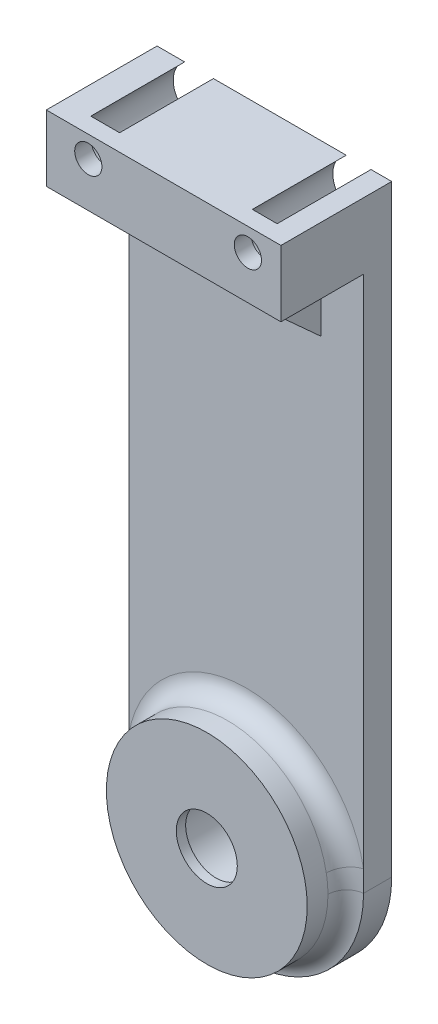
SolidWorks part; units mm, degrees
ref_plane "Plano frontal" through (0, 0, 0) normal (0, 0, 1) x (1, 0, 0)
ref_plane "Plano superior" through (0, 0, 0) normal (0, 1, 0) x (1, 0, 0)
ref_plane "Plano direito" through (0, 0, 0) normal (1, 0, 0) x (0, 0, -1)
ref_plane "Plano1" through (0, 0, -1.35) normal (0, 0, 1) x (1, 0, 0)
sketch "Esboço2" plane through (0, 0, -1.35) normal (0, 0, 1) x (1, 0, 0)
  circle A5 centre (-0.4749, -0.0634) radius 10.7 construction
  circle A6 centre (-0.4749, -0.0634) radius 10.7
extrude "Ressalto-extrusão1" add sketch "Esboço2" against normal offset from surface (4.2 mm away) 2 offset beyond the face yes
sketch "Esboço4" plane through (0, 0, -5.55) normal (0, 0, -1) x (-1, 0, 0)
  line L0 (-12.0251, -0.0634) -> (-12.0251, 64.1202)
  line L1 (12.9749, -0.0634) -> (12.9749, 64.1202)
  line L2 (12.9749, 64.1202) -> (-12.0251, 64.1202)
  arc A0 (-12.0251, -0.0634) -> (12.9749, -0.0634) centre (0.4749, -0.0634) ccw
  arc A2 (-12.0247, -0.1594) -> (12.9746, 0.0325) centre (0.4749, -0.0634) ccw construction
  dimension "D1" = 0.5
extrude "Ressalto-extrusão3" add sketch "Esboço4" along normal blind 3
sketch "Esboço5" plane through (0, 0, -8.55) normal (0, 0, -1) x (-1, 0, 0)
  line L0 (12.9749, -0.0634) -> (12.9749, 64.1202) construction
  line L1 (-12.0251, 64.1202) -> (12.9749, 64.1202)
  line L2 (-12.0251, 64.1202) -> (-12.0251, 57.0691)
  line L3 (-12.0251, 57.0691) -> (12.9749, 57.0691)
  line L5 (12.9749, 57.0691) -> (12.9749, 64.1202)
extrude "Ressalto-extrusão4" add sketch "Esboço5" against normal up to surface (11.8 mm away)
hole_wizard "Rebaixo para SHCS M2.51" positions "Esboço6" profile "Esboço7" counterbore size "M2.5" standard "Ansi Metric" end condition up to next
sketch "Esboço6" plane through (0, 0, -8.55) normal (0, 0, -1) x (-1, 0, 0)
  circle A0 centre (-8.4995, 61.7078) radius 1.35 construction
  circle A1 centre (8.5, 61.8383) radius 1.35 construction
  point P0 (-8.4995, 61.7078)
  point P2 (8.5, 61.8383)
sketch "Esboço7" plane through (8.4995, 61.7078, -8.55) normal (1, 0, 0) x (0, 1, 0)
  line L0 (0, 0) -> (0, 11.8)
  line L1 (0, 11.8) -> (1.45, 11.8)
  line L3 (1.45, 11.8) -> (1.45, 10)
  line L4 (1.45, 10) -> (2.75, 10)
  line L5 (2.75, 10) -> (2.75, 0)
  line L7 (2.75, 0) -> (0, 0)
  line L11 (0, -6.35) -> (0, 107.95) construction
  dimension "Thru Hole Dia." = 2.9
  dimension "Thru Hole Depth" = 11.8
  dimension "C'Bore Dia." = 5.5
  dimension "C'Bore Depth" = 10
sketch "Esboço10" plane through (0, 0, 0) normal (1, 0, 0) x (0, 0, -1)
  line L0 (-3.25, 57.0691) -> (5.55, 49.0691)
  line L1 (5.55, -0.0634) -> (5.55, 57.0691) construction
  line L2 (-3.25, 57.0691) -> (5.55, 57.0691) construction
  dimension "D1" = 8
rib "Nervura1" sketch "Esboço10" sketch "Esboço10" thickness 15 extrusion direction parallel to sketch draft on no parameters "D1"=15
sketch "Esboço11" plane through (0, 0, -5.55) normal (0, 0, 1) x (1, 0, 0)
  line L0 (7.5, 49.0691) -> (-7.5, 49.0691) construction
  line L1 (4.5, 49.0691) -> (-4.5, 49.0691)
  line L2 (4.5, 49.0691) -> (4.5, 57.0691)
  line L3 (4.5, 57.0691) -> (-4.5, 57.0691)
  line L4 (-4.5, 49.0691) -> (-4.5, 57.0691)
  line L5 (7.5, 57.0691) -> (-7.5, 57.0691) construction
  line L6 (7.5, 57.0691) -> (7.5, 49.0691) construction
  point P8 (0, 57.0691)
  point P9 (0, 57.0691)
  dimension "D1" = 3
extrude "Corte-extrusão1" cut sketch "Esboço11" along normal up to next
sketch "Esboço12" plane through (0, 0, -8.55) normal (0, 0, -1) x (-1, 0, 0)
  circle A0 centre (0.4749, -0.0634) radius 3.25 construction
  circle A1 centre (0.4749, -0.0634) radius 3.25
extrude "Corte-extrusão2" cut sketch "Esboço12" against normal through all
sketch "Esboço13" plane through (0, 0, -8.55) normal (0, 0, -1) x (-1, 0, 0)
  circle A0 centre (0.4749, -0.0634) radius 4 construction
  circle A1 centre (0.4749, -0.0634) radius 4
extrude "Corte-extrusão3" cut sketch "Esboço13" against normal offset from surface (6.2 mm away) 1 up to face at (2.7751, -0.0634, -1.35)
fillet "Filete1" radius 2 1 edges at (-0.4749, 10.6366, -5.55)
